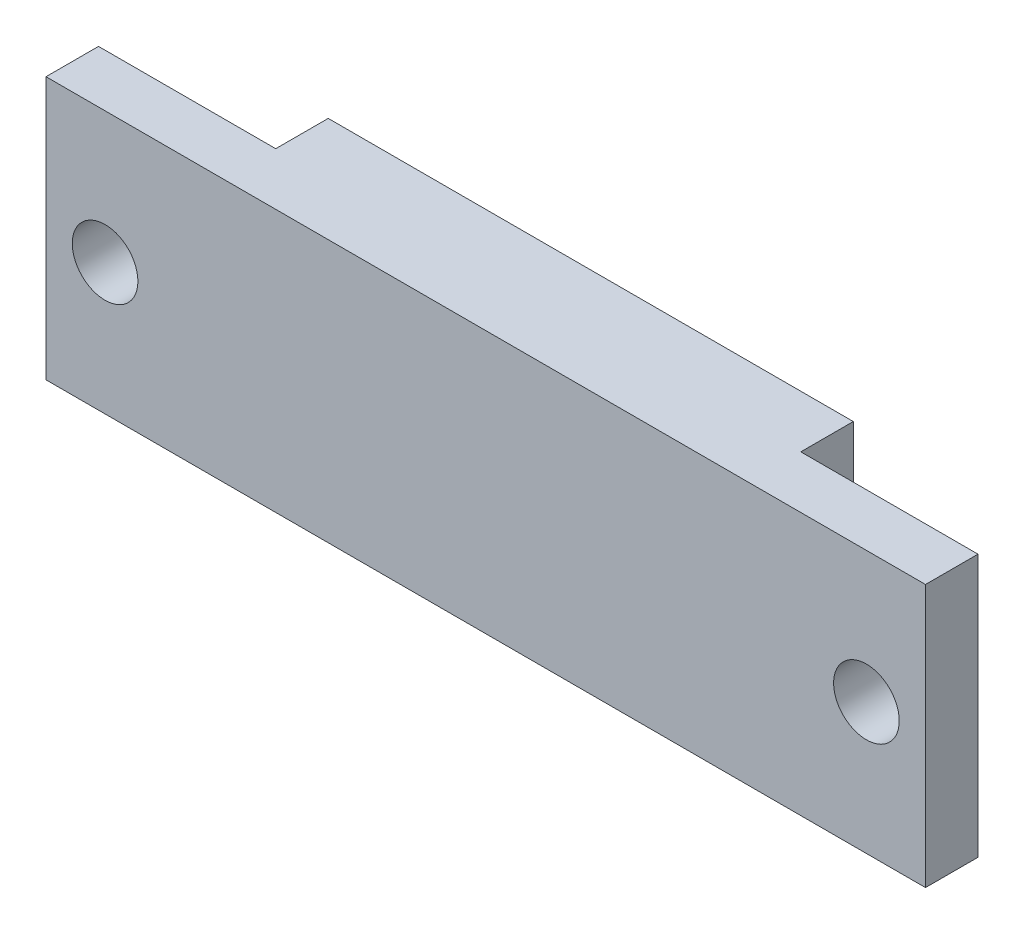
SolidWorks part; units mm, degrees
ref_plane "Front Plane" through (0, 0, 0) normal (0, 0, 1) x (1, 0, 0)
ref_plane "Top Plane" through (0, 0, 0) normal (0, 1, 0) x (1, 0, 0)
ref_plane "Right Plane" through (0, 0, 0) normal (1, 0, 0) x (0, 0, -1)
sketch "Sketch1" plane through (0, 0, 0) normal (0, 1, 0) x (1, 0, 0)
  line L0 (67.945, 0) -> (85.09, 0)
  line L1 (0, 0) -> (17.145, 0)
  line L2 (0, 0) -> (0, -5.08)
  line L3 (0, -5.08) -> (85.09, -5.08)
  line L4 (85.09, 0) -> (85.09, -5.08)
  line L6 (17.145, 0) -> (17.145, 5.08)
  line L7 (17.145, 5.08) -> (67.945, 5.08)
  line L8 (67.945, 0) -> (67.945, 5.08)
  dimension "D1" = 50.8
  dimension "D2" = 5.08
  dimension "D3" = 85.09
  dimension "D4" = 5.08
extrude "Boss-Extrude1" add sketch "Sketch1" along normal blind 25.4
hole_wizard "1/4 (0.25) Diameter Hole1" positions "Sketch2" profile "Sketch3" hole size "1/4" standard "ANSI Inch" end condition through all
sketch "Sketch2" plane through (0, 0, 5.08) normal (0, 0, 1) x (1, 0, 0)
  line L2 (42.545, 0) -> (42.545, 25.4) construction
  line L3 (0, 0) -> (85.09, 0) construction
  line L4 (0, 25.4) -> (85.09, 25.4) construction
  line L6 (5.715, 12.7) -> (79.375, 12.7) construction
  point P0 (5.715, 12.7)
  point P2 (79.375, 12.7)
  point P25 (42.545, 12.7)
  point P26 (42.545, 12.7)
  dimension "D1" = 73.66
sketch "Sketch3" plane through (5.715, 12.7, 5.08) normal (1, 0, 0) x (0, -1, 0)
  line L0 (0, 0) -> (0, 10.16)
  line L1 (0, 10.16) -> (3.175, 10.16)
  line L2 (3.175, 10.16) -> (3.175, 0)
  line L5 (3.175, 0) -> (0, 0)
  line L11 (0, -6.35) -> (0, 107.95) construction
  dimension "Thru Hole Dia." = 6.35
  dimension "Thru Hole Depth" = 10.16
